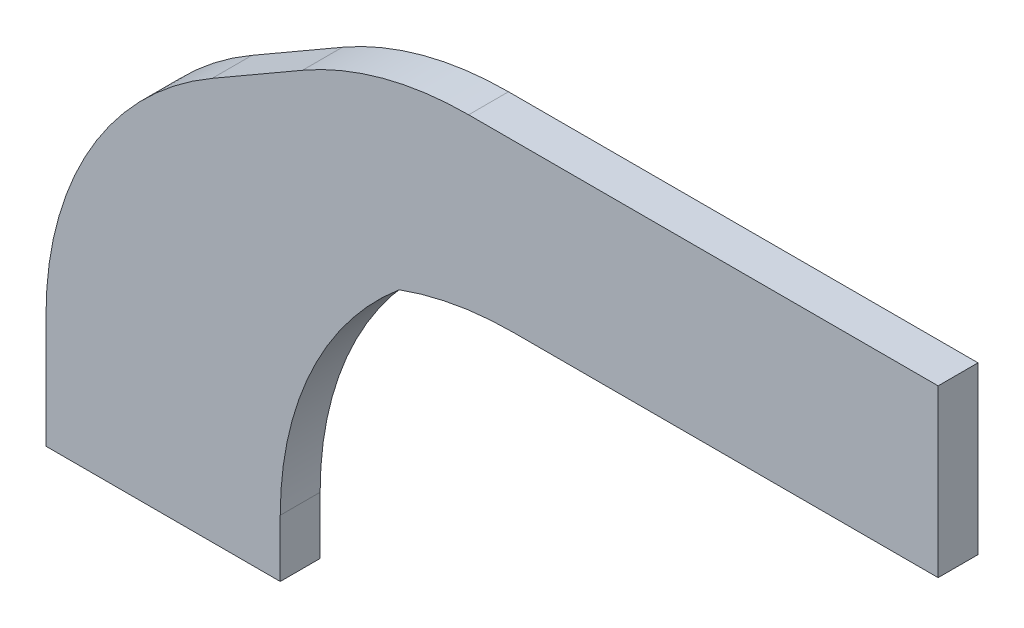
SolidWorks part; units mm, degrees
material "PBT General Purpose"
ref_plane "Front Plane" through (0, 0, 0) normal (0, 0, 1) x (1, 0, 0)
ref_plane "Top Plane" through (0, 0, 0) normal (0, 1, 0) x (1, 0, 0)
ref_plane "Right Plane" through (0, 0, 0) normal (1, 0, 0) x (0, 0, -1)
sketch "Sketch1" plane through (0, 0, 0) normal (0, 0, 1) x (1, 0, 0)
  line L7 (0, 0) -> (1.41, 0)
  line L8 (1.41, 0) -> (1.41, 1.5)
  line L9 (1.41, 1.5) -> (2.276, 2)
  line L10 (2.276, 2) -> (5.37, 2)
  line L11 (5.37, 2) -> (5.37, 3)
  line L12 (5.37, 3) -> (2.0081, 3)
  line L13 (2.0081, 3) -> (0, 1.8406)
  line L14 (0, 1.8406) -> (0, 0)
  dimension "D1" = 1.41
  dimension "D2" = 1
  dimension "D3" = 1.5
  dimension "D4" = 3.96
  dimension "D5" = 1
  dimension "D6" = 3
  dimension "D7" = 1
extrude "Boss-Extrude1" add sketch "Sketch1" along normal mid plane 0.24 contours L10 L11 L12 L13 L14 L7 L8 L9
fillet "Fillet1" radius 2 4 edges at (1.41, 1.5, 0) (2.276, 2, 0) (2.0081, 3, 0) (0, 1.8406, 0)
